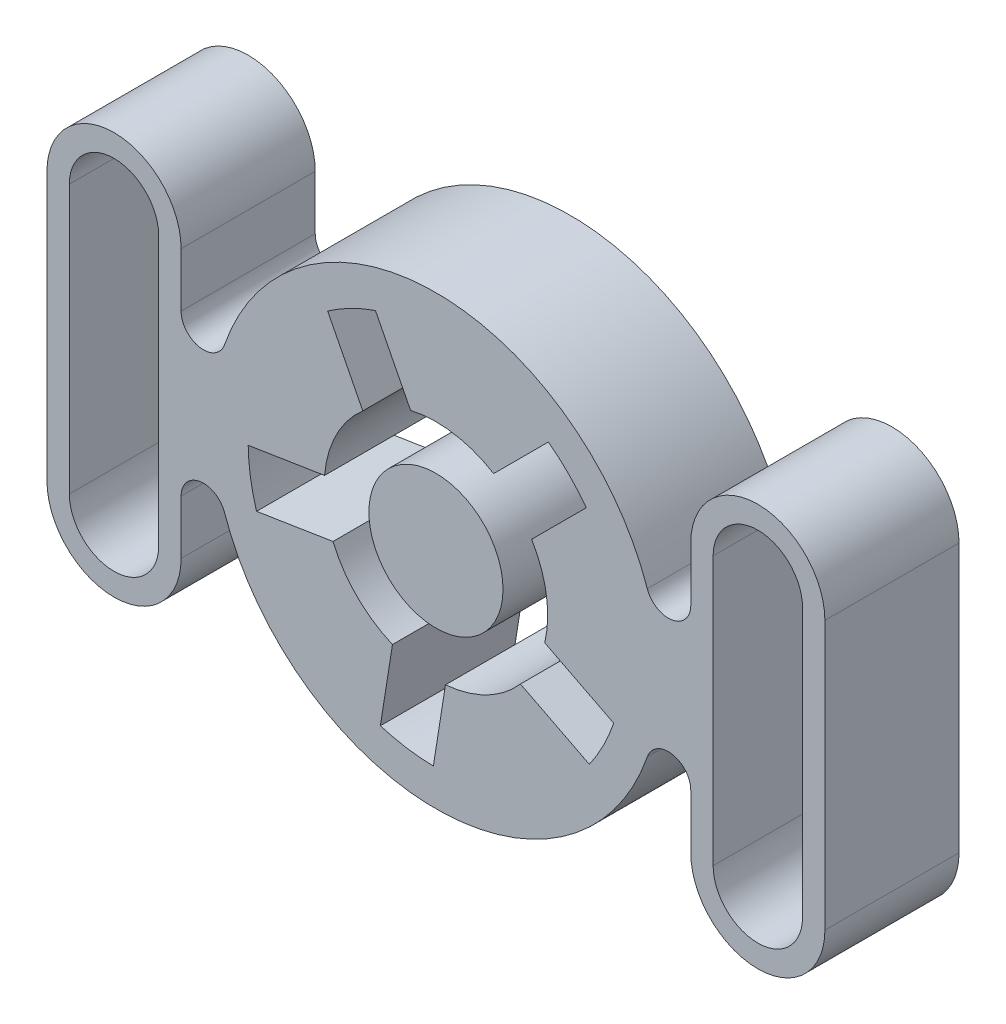
SolidWorks part; units mm, degrees
ref_plane "Front Plane" through (0, 0, 0) normal (0, 0, 1) x (1, 0, 0)
ref_plane "Top Plane" through (0, 0, 0) normal (0, 1, 0) x (1, 0, 0)
ref_plane "Right Plane" through (0, 0, 0) normal (1, 0, 0) x (0, 0, -1)
sketch "Sketch1" plane through (0, 0, 0) normal (0, 0, 1) x (1, 0, 0)
  line L0 (0, 0) -> (44610.632, 0) construction
  line L1 (0, 0) -> (0, -44610.632) construction
  line L2 (777.8175, 777.8175) -> (35.3553, 35.3553) construction
  line L3 (12.9184, 21.4036) -> (25.1512, 33.6365)
  line L5 (29.6985, 29.6985) -> (-35.3553, -35.3553) construction
  line L6 (33.6365, 25.1512) -> (21.4036, 12.9184)
  line L7 (24.3481, -5.672) -> (39.7624, -13.526)
  line L8 (34.3145, -24.2181) -> (18.9002, -16.3641)
  line L9 (2.1296, -24.9091) -> (-0.5767, -41.996)
  line L10 (-12.429, -40.1188) -> (-9.7227, -23.0319)
  line L11 (-23.0319, -9.7227) -> (-40.1188, -12.429)
  line L12 (-41.996, -0.5767) -> (-24.9091, 2.1296)
  line L13 (-16.3641, 18.9002) -> (-24.2181, 34.3145)
  line L14 (-13.526, 39.7624) -> (-5.672, 24.3481)
  line L15 (72, 30) -> (72, -30) construction
  line L16 (82, 30) -> (82, -30)
  line L17 (62, 30) -> (62, -30)
  line L18 (72, 30) -> (72, -30) construction
  line L19 (87, 30) -> (87, -30)
  line L20 (57, 30) -> (57, -30)
  line L21 (-72, 30) -> (-72, -30) construction
  line L22 (-82, 30) -> (-82, -30)
  line L23 (-62, 30) -> (-62, -30)
  line L24 (-72, 30) -> (-72, -30) construction
  line L25 (-87, 30) -> (-87, -30)
  line L26 (-57, 30) -> (-57, -30)
  circle A0 centre (0, 0) radius 15
  arc A1 (12.9184, 21.4036) -> (-5.672, 24.3481) centre (0, 0) ccw
  circle A2 centre (0, 0) radius 42 construction
  arc A3 (47.2727, 16.2877) -> (-47.2727, 16.2877) centre (0, 0) ccw
  arc A4 (25.1512, 33.6365) -> (33.6365, 25.1512) centre (0, 0) cw
  arc A5 (39.7624, -13.526) -> (34.3145, -24.2181) centre (0, 0) cw
  arc A6 (-0.5767, -41.996) -> (-12.429, -40.1188) centre (0, 0) cw
  arc A7 (-40.1188, -12.429) -> (-41.996, -0.5767) centre (0, 0) cw
  arc A8 (-24.2181, 34.3145) -> (-13.526, 39.7624) centre (0, 0) cw
  arc A9 (-16.3641, 18.9002) -> (-24.9091, 2.1296) centre (0, 0) ccw
  arc A10 (-23.0319, -9.7227) -> (-9.7227, -23.0319) centre (0, 0) ccw
  arc A11 (2.1296, -24.9091) -> (18.9002, -16.3641) centre (0, 0) ccw
  arc A12 (24.3481, -5.672) -> (21.4036, 12.9184) centre (0, 0) ccw
  arc A13 (82, 30) -> (62, 30) centre (72, 30) ccw
  arc A14 (62, -30) -> (82, -30) centre (72, -30) ccw
  arc A15 (87, 30) -> (57, 30) centre (72, 30) ccw
  arc A16 (57, -30) -> (87, -30) centre (72, -30) ccw
  arc A17 (47.2727, -16.2877) -> (57, -17.9165) centre (52, -17.9165) cw
  arc A18 (47.2727, 16.2877) -> (57, 17.9165) centre (52, 17.9165) ccw
  arc A19 (-47.2727, -16.2877) -> (-57, -17.9165) centre (-52, -17.9165) ccw
  arc A20 (-47.2727, 16.2877) -> (-57, 17.9165) centre (-52, 17.9165) cw
  arc A21 (-82, 30) -> (-62, 30) centre (-72, 30) cw
  arc A22 (-62, -30) -> (-82, -30) centre (-72, -30) cw
  arc A23 (-87, 30) -> (-57, 30) centre (-72, 30) cw
  arc A24 (-57, -30) -> (-87, -30) centre (-72, -30) cw
  arc A25 (-47.2727, -16.2877) -> (47.2727, -16.2877) centre (0, 0) ccw
  point P7 (72, 0)
  point P41 (0, 0)
  point P46 (72, 0)
  point P66 (-72, 0)
  point P73 (-72, 0)
  dimension "D1" = 30
  dimension "D2" = 50
  dimension "D3" = 100
  dimension "84" = 84
  dimension "D9" = 15
  dimension "D10" = 10
  dimension "D11" = 5
  dimension "D4" = 45
  dimension "D5" = 12
  dimension "D6" = 5
  dimension "D7" = 60
  dimension "D8" = 72
extrude "Boss-Extrude1" add sketch "Sketch1" along normal mid plane 30 contours A0 region at (0, 0, 0)
extrude "Boss-Extrude2" add sketch "Sketch1<3>" along normal mid plane 30 separate body contours A19 A25 A17 L20 A18 A3 A20 L26 A12 L7 A5 L8 A11 L9 A6 L10 A10 L11 A7 L12 A9 L13 A8 L14 A1 L3 A4 L6 region at (55.4836, 0, 0)
sketch "Sketch1<3>" plane through (0, 0, 0) normal (0, 0, 1) x (1, 0, 0) same geometry as "Sketch1"
extrude "Boss-Extrude3" add sketch "Sketch1<4>" along normal mid plane 30 contours A24 L26 A23 L25 L23 A22 L22 A21 | L20 A16 L19 A15 A14 L17 A13 L16 region at (86.0513, 0, 0) region at (-57.9487, 0, 0)
sketch "Sketch1<4>" plane through (0, 0, 0) normal (0, 0, 1) x (1, 0, 0) same geometry as "Sketch1"
